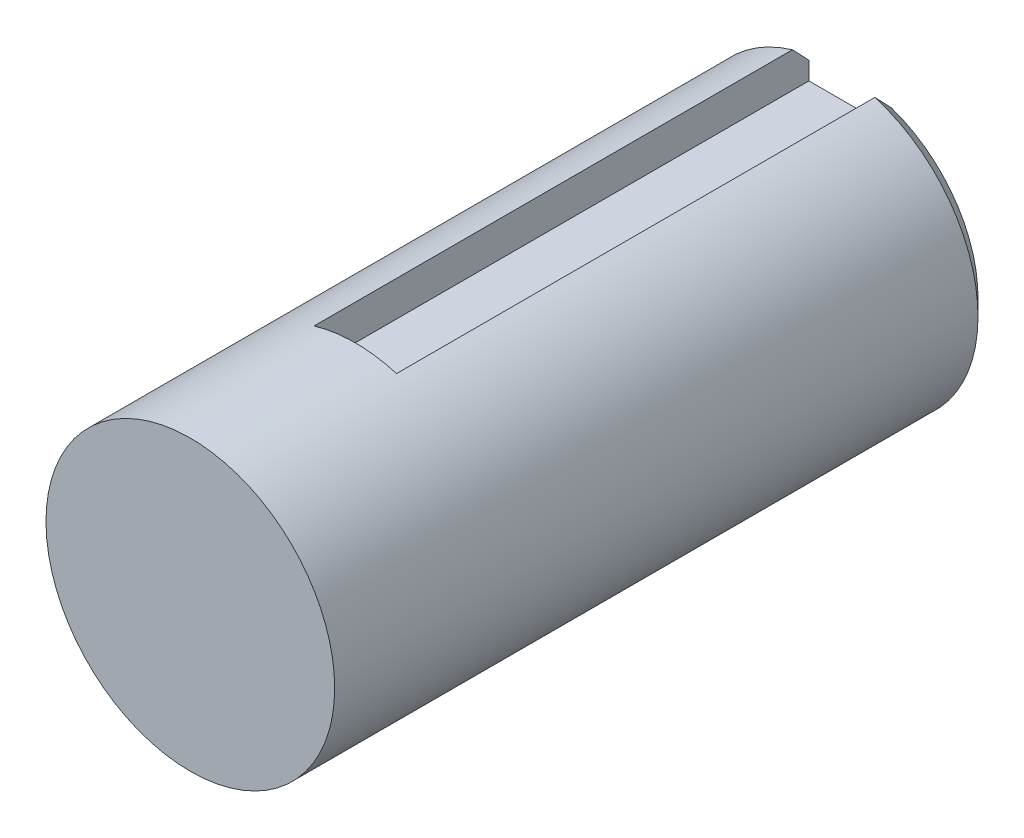
SolidWorks part; units mm, degrees
material "Ductile Iron"
ref_plane "Front Plane" through (0, 0, 0) normal (0, 0, 1) x (1, 0, 0)
ref_plane "Top Plane" through (0, 0, 0) normal (0, 1, 0) x (1, 0, 0)
ref_plane "Right Plane" through (0, 0, 0) normal (1, 0, 0) x (0, 0, -1)
sketch "Sketch1" plane through (0, 0, 0) normal (0, 0, 1) x (1, 0, 0)
  line L0 (0, 0) -> (0, 17.5) construction
  line L1 (-5, 12.5) -> (5, 12.5)
  line L2 (0, 0) -> (0, -17.5)
  line L3 (-5, 12.5) -> (-5, 16.7705)
  line L4 (5, 12.5) -> (5, 16.7705)
  arc A0 (-5, 16.7705) -> (5, 16.7705) centre (0, 0) ccw
  point P8 (0, 12.5)
  dimension "D1" = 35
  dimension "D2" = 30
  dimension "D3" = 10
extrude "Boss-Extrude1" add sketch "Sketch1" along normal blind 80 contours A0 L4 L1 L3
sketch "Sketch2" plane through (0, 0, 80) normal (0, 0, 1) x (1, 0, 0)
  line L0 (5, 12.5) -> (5, 16.7705) construction
  line L1 (-5, 12.5) -> (5, 12.5) construction
  line L2 (-5, 12.5) -> (-5, 16.7705) construction
  line L3 (5, 12.5) -> (5, 16.7705)
  line L4 (-5, 12.5) -> (5, 12.5)
  line L5 (-5, 12.5) -> (-5, 16.7705)
  arc A0 (-5, 16.7705) -> (5, 16.7705) centre (0, 0) cw
  arc A1 (-5, 16.7705) -> (5, 16.7705) centre (0, 0) ccw construction
extrude "Boss-Extrude2" add sketch "Sketch2" against normal blind 20
chamfer "Chamfer1" distance 2 angle 45 1 edges at (0, -17.5, 0)
